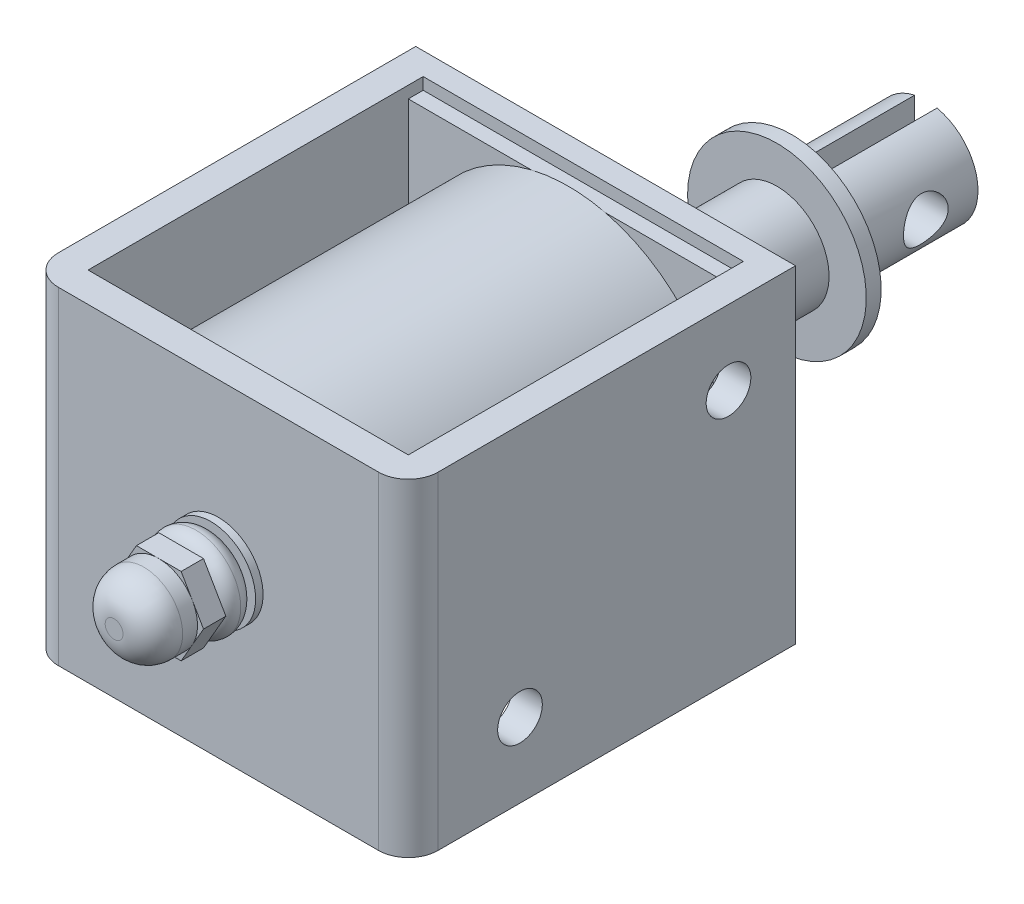
SolidWorks part; units mm, degrees
ref_plane "Front Plane" through (0, 0, 0) normal (0, 0, 1) x (1, 0, 0)
ref_plane "Top Plane" through (0, 0, 0) normal (0, 1, 0) x (1, 0, 0)
ref_plane "Right Plane" through (0, 0, 0) normal (1, 0, 0) x (0, 0, -1)
sketch "Sketch2" plane through (0, 0, 0) normal (0, 1, 0) x (1, 0, 0)
  line L1 (-12.75, -13) -> (12.75, -13)
  line L2 (-12.75, -13) -> (-12.75, 13)
  line L3 (-12.75, 13) -> (12.75, 13)
  line L4 (12.75, -13) -> (12.75, 13)
  line L5 (-12.75, -13) -> (12.75, 13) construction
  line L6 (-12.75, 13) -> (12.75, -13) construction
  point P0 (0, 0)
  dimension "D1" = 25.5
  dimension "D2" = 26
extrude "Boss-Extrude1" add sketch "Sketch2" along normal blind 22
fillet "Fillet1" radius 2 2 edges at (12.75, 11, 13) (-12.75, 11, 13)
sketch "Sketch3" plane through (0, 22, 0) normal (0, 1, 0) x (1, 0, 0)
  line L0 (12.75, -11) -> (12.75, 13) construction
  line L1 (-10.75, -11) -> (10.75, -11)
  line L2 (-10.75, -11) -> (-10.75, 11.5)
  line L3 (-10.75, 11.5) -> (10.75, 11.5)
  line L4 (10.75, -11) -> (10.75, 11.5)
  line L5 (-10.75, -13) -> (10.75, -13) construction
  line L6 (-12.75, 13) -> (-12.75, -11) construction
  line L7 (12.75, 13) -> (-12.75, 13) construction
  point P0 (0, 0)
  dimension "D1" = 2
  dimension "D2" = 1.5
  dimension "D3" = 2
  dimension "D4" = 2
extrude "Cut-Extrude1" cut sketch "Sketch3" against normal up to surface (22 mm away) up to face at (0, 0, 3.8047)
sketch "Sketch4" plane through (0, 0, -11.5) normal (0, 0, 1) x (1, 0, 0)
  line L0 (10.75, 0) -> (10.75, 22) construction
  line L1 (-10.75, 0.8) -> (10.75, 0.8)
  line L2 (-10.75, 0.8) -> (-10.75, 21.2)
  line L3 (-10.75, 21.2) -> (10.75, 21.2)
  line L4 (10.75, 0.8) -> (10.75, 21.2)
  line L5 (-10.75, 0.8) -> (10.75, 21.2) construction
  line L6 (-10.75, 21.2) -> (10.75, 0.8) construction
  line L7 (-10.75, 22) -> (10.75, 22) construction
  line L8 (-10.75, 0) -> (10.75, 0) construction
  point P0 (0, 11)
  dimension "D1" = 0.8
  dimension "D2" = 0.8
  dimension "D3" = 21.5
extrude "Boss-Extrude2" add sketch "Sketch4" along normal blind 1
sketch "Sketch5" plane through (0, 0, -10.5) normal (0, 0, 1) x (1, 0, 0)
  line L0 (-10.75, 22) -> (10.75, 22) construction
  line L1 (-10.75, 22) -> (-10.75, 0) construction
  circle A0 centre (0, 11) radius 10.5
  dimension "D2" = 21
  dimension "D1" = 11
  dimension "D3" = 10.75
extrude "Boss-Extrude3" add sketch "Sketch5" along normal up to surface (21.5 mm away) up to face at (0, 11, 11)
sketch "Sketch7" plane through (0, 0, 13) normal (0, 0, 1) x (1, 0, 0)
  line L0 (-10.75, 22) -> (10.75, 22) construction
  line L1 (10.75, 0) -> (10.75, 22) construction
  circle A0 centre (0, 11) radius 3
  dimension "D1" = 11
  dimension "D2" = 10.75
  dimension "'6" = 6
extrude "Boss-Extrude4" add sketch "Sketch7" along normal blind 0.5
sketch "Sketch8" plane through (0, 0, 13.5) normal (0, 0, 1) x (1, 0, 0)
  circle A0 centre (0, 11) radius 3
  dimension "D1" = 6
extrude "Boss-Extrude5" add sketch "Sketch8" along normal blind 2
extrude "Cut-Extrude2" cut sketch "Sketch7<3>" along normal blind 0.5
sketch "Sketch7<3>" plane through (0, 0, 13) normal (0, 0, 1) x (1, 0, 0) same geometry as "Sketch7"
fillet "Fillet2" radius 1 1 edges at (3, 11, 13.5)
fillet "Fillet3" radius 1 1 edges at (3, 11, 15.5)
extrude "Boss-Extrude6" add sketch "Sketch7<4>" along normal blind 0.5
sketch "Sketch7<4>" plane through (0, 0, 13) normal (0, 0, 1) x (1, 0, 0) same geometry as "Sketch7"
sketch "Sketch9" plane through (0, 0, 15.5) normal (0, 0, 1) x (1, 0, 0)
  line L1 (3.0022, 11) -> (1.5011, 13.6)
  line L2 (1.5011, 13.6) -> (-1.5011, 13.6)
  line L3 (-1.5011, 13.6) -> (-3.0022, 11)
  line L4 (-3.0022, 11) -> (-1.5011, 8.4)
  line L5 (-1.5011, 8.4) -> (1.5011, 8.4)
  line L6 (1.5011, 8.4) -> (3.0022, 11)
  circle A0 centre (0, 11) radius 2.6 construction
  dimension "D1" = 5.2
extrude "Boss-Extrude7" add sketch "Sketch9" along normal blind 1.5
sketch "Sketch10" plane through (0, 0, 17) normal (0, 0, 1) x (1, 0, 0)
  line L0 (-10.75, 22) -> (10.75, 22) construction
  line L1 (12.75, 22) -> (12.75, 0) construction
  circle A0 centre (0, 11) radius 2.6
  dimension "D1" = 11
  dimension "D2" = 12.75
  dimension "D3" = 5.2
extrude "Boss-Extrude8" add sketch "Sketch10" along normal blind 3
fillet "Fillet4" radius 2 1 edges at (2.6, 11, 20)
sketch "Sketch11" plane through (0, 0, -13) normal (0, 0, -1) x (-1, 0, 0)
  line L0 (-12.75, 22) -> (12.75, 22) construction
  line L1 (12.75, 22) -> (12.75, 0) construction
  circle A0 centre (0, 11) radius 3.5
  dimension "D1" = 11
  dimension "D2" = 7
  dimension "D3" = 12.75
extrude "Boss-Extrude9" add sketch "Sketch11" along normal blind 11.5
sketch "Sketch12" plane through (0, 0, -24.5) normal (0, 0, -1) x (-1, 0, 0)
  circle A0 centre (0, 11) radius 6
  dimension "D1" = 12
extrude "Boss-Extrude10" add sketch "Sketch12" along normal blind 1
sketch "Sketch13" plane through (0, 0, -25.5) normal (0, 0, -1) x (-1, 0, 0)
  circle A0 centre (0, 11) radius 3.5
  dimension "D1" = 7
extrude "Boss-Extrude11" add sketch "Sketch13" along normal blind 9
sketch "Sketch15" plane through (0, 0, -34.5) normal (0, 0, -1) x (-1, 0, 0)
  line L1 (-0.75, 7.5) -> (0.75, 7.5)
  line L2 (-0.75, 7.5) -> (-0.75, 14.5)
  line L3 (-0.75, 14.5) -> (0.75, 14.5)
  line L4 (0.75, 7.5) -> (0.75, 14.5)
  line L5 (-0.75, 7.5) -> (0.75, 14.5) construction
  line L6 (-0.75, 14.5) -> (0.75, 7.5) construction
  point P0 (0, 11)
  dimension "D1" = 7
  dimension "D2" = 1.5
extrude "Cut-Extrude3" cut sketch "Sketch15" against normal blind 8
sketch "Sketch16" plane through (0.75, 0, 0) normal (-1, 0, 0) x (0, 0, 1)
  line L0 (-34.5, 14.4187) -> (-34.5, 7.5813) construction
  line L1 (-26.5, 14.4187) -> (-34.5, 14.4187) construction
  circle A0 centre (-31, 10.9223) radius 1.5
  dimension "D1" = 3
  dimension "D2" = 3.5
  dimension "D3" = 3.4964
extrude "Cut-Extrude4" cut sketch "Sketch16" against normal blind 5 and the other way blind 5
sketch "Sketch17" plane through (0, 0, -13) normal (0, 0, -1) x (-1, 0, 0)
  circle A0 centre (0, 11) radius 5
  dimension "D1" = 10
extrude "Cut-Extrude5" cut sketch "Sketch17" against normal blind 2
sketch "Sketch18" plane through (0, 0, -11) normal (0, 0, -1) x (-1, 0, 0)
  circle A0 centre (0, 11) radius 5
extrude "Boss-Extrude14" add sketch "Sketch18" along normal blind 2.1
sketch "Sketch19" plane through (12.75, 0, 0) normal (1, 0, 0) x (0, 0, -1)
  line L0 (-11, 0) -> (13, 0) construction
  line L1 (-11, 22) -> (13, 22) construction
  line L2 (-13, 0) -> (-13, 22) construction
  line L4 (13, 22) -> (13, 0) construction
  circle A0 centre (-5.5, 5) radius 1.5
  circle A1 centre (8.5, 17) radius 1.5
  dimension "D1" = 3
  dimension "D2" = 3
  dimension "D3" = 4.5
  dimension "D4" = 5
  dimension "D5" = 5
  dimension "D6" = 7.5
extrude "Cut-Extrude6" cut sketch "Sketch19" against normal up to surface (2 mm away) up to face at (10.75, 11, -5.625)
